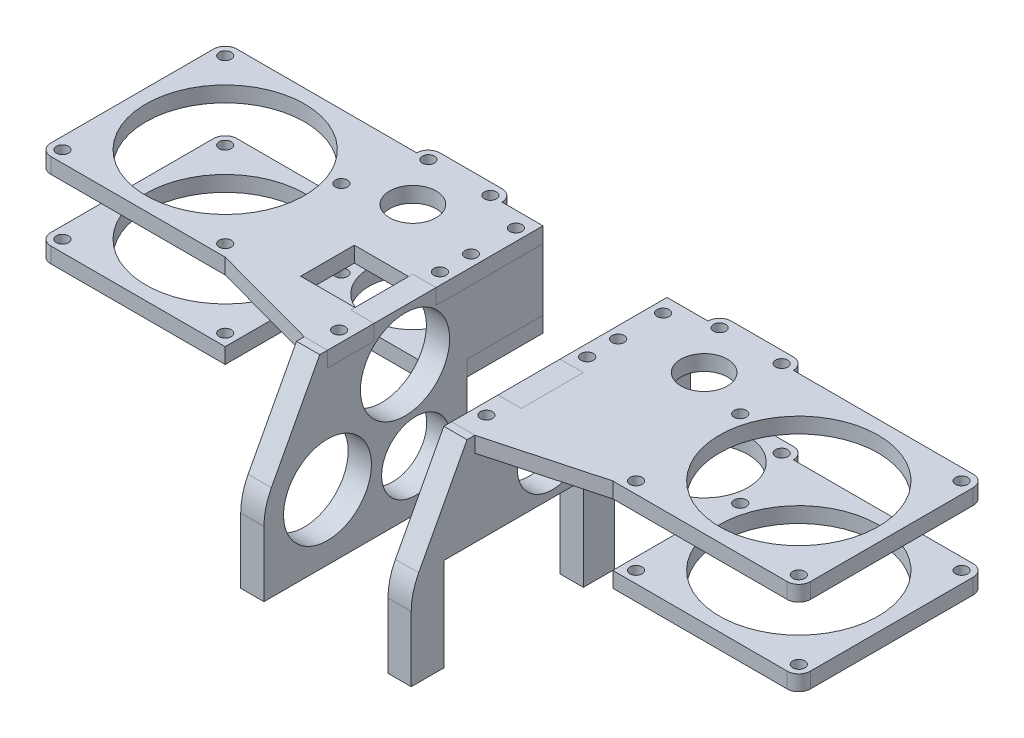
SolidWorks part; units mm, degrees
material "Alum Plate"
ref_plane "Front Plane" through (0, 0, 0) normal (0, 0, 1) x (1, 0, 0)
ref_plane "Top Plane" through (0, 0, 0) normal (0, 1, 0) x (1, 0, 0)
ref_plane "Right Plane" through (0, 0, 0) normal (1, 0, 0) x (0, 0, -1)
sketch "Sketch1" plane through (0, 0, 0) normal (0, 1, 0) x (1, 0, 0)
  line L0 (0, 0) -> (117.475, 0) construction
  line L1 (-117.475, 0) -> (0, 0) construction
  line L3 (-9.525, 165.735) -> (-3.175, 165.735)
  line L4 (-9.525, 165.735) -> (-9.525, 51.435)
  line L5 (-9.525, 51.435) -> (-3.175, 51.435)
  line L6 (-3.175, 165.735) -> (-3.175, 51.435)
  line L7 (-9.525, 165.735) -> (-3.175, 51.435) construction
  line L8 (-9.525, 51.435) -> (-3.175, 165.735) construction
  line L14 (-155.575, -76.2) -> (155.575, -76.2)
  line L20 (-25.4, 38.1) -> (0, 38.1) construction
  line L21 (-6.35, 108.585) -> (0, 108.585)
  line L29 (0, 0) -> (0, -18.415) construction
  line L30 (-117.475, 0) -> (-59.6589, 19.05) construction
  line L43 (59.6589, 19.05) -> (117.475, 0) construction
  line L44 (-86.6074, 10.1707) -> (-86.2044, 10.3034)
  line L55 (-77.1578, 13.2842) -> (-76.7548, 13.417)
  line L69 (-155.575, -76.2) -> (-155.575, 38.1)
  line L70 (-155.575, 38.1) -> (155.575, 38.1)
  line L71 (155.575, -76.2) -> (155.575, 38.1)
  line L78 (0, 108.585) -> (0, -18.415)
  line L79 (0, -18.415) -> (0, -145.415) construction
  line L80 (-9.525, -202.565) -> (-3.175, -202.565) construction
  line L81 (-9.525, -202.565) -> (-9.525, -88.265) construction
  line L82 (-9.525, -88.265) -> (-3.175, -88.265) construction
  line L83 (-3.175, -202.565) -> (-3.175, -88.265) construction
  line L84 (-9.525, -202.565) -> (-3.175, -88.265) construction
  line L85 (-9.525, -88.265) -> (-3.175, -202.565) construction
  line L86 (0, -145.415) -> (-6.35, -145.415) construction
  line L87 (-34.925, -76.2) -> (-25.4, -76.2)
  line L88 (-34.925, -76.2) -> (-34.925, 38.1)
  line L89 (-34.925, 38.1) -> (-25.4, 38.1)
  line L90 (-25.4, -76.2) -> (-25.4, 38.1)
  line L91 (34.925, -76.2) -> (25.4, -76.2)
  line L92 (34.925, -76.2) -> (34.925, 38.1)
  line L93 (34.925, 38.1) -> (25.4, 38.1)
  line L94 (25.4, -76.2) -> (25.4, 38.1)
  line L95 (0, 38.1) -> (25.4, 38.1) construction
  circle A0 centre (-117.475, 0) radius 32.5
  circle A1 centre (-117.475, 0) radius 25
  circle A2 centre (117.475, 0) radius 32.5
  circle A3 centre (117.475, 0) radius 25
  circle A4 centre (-59.6589, 19.05) radius 18
  circle A5 centre (59.6589, 19.05) radius 18
  circle A8 centre (-81.6811, 11.7938) radius 4.7625
  point P8 (-6.35, 108.585)
  point P21 (117.475, 32.5)
  point P25 (59.6589, 37.05)
  point P29 (59.6589, 1.05)
  point P31 (0, -76.2)
  point P32 (-6.35, -145.415)
  point P62 (149.975, 0)
  dimension "D1" = 50
  dimension "D2" = 65
  dimension "D8" = 36
  dimension "D11" = 127
  dimension "D12" = 56.515
  dimension "D16" = 9.525
  dimension "D3" = 114.3
  dimension "D4" = 6.35
  dimension "D5" = 234.95
  dimension "D6" = 38.1
  dimension "D7" = 38.1
  dimension "D9" = 114.3
  dimension "D10" = 9.525
  dimension "D13" = 9.525
  dimension "D14" = 50.8
  dimension "D15" = 60.8736
  dimension "D18" = 19.05
sketch "Sketch2" plane through (0, 0, 0) normal (1, 0, 0) x (0, 0, -1)
  line L0 (0, 25.4) -> (0, 56.175) construction
  line L1 (-32.5, 59.675) -> (32.5, 59.675)
  line L2 (-32.5, 59.675) -> (-32.5, 52.675)
  line L3 (-32.5, 52.675) -> (32.5, 52.675)
  line L4 (32.5, 59.675) -> (32.5, 52.675)
  line L5 (-32.5, 59.675) -> (32.5, 52.675) construction
  line L6 (-32.5, 52.675) -> (32.5, 59.675) construction
  line L7 (-32.5, 88.9) -> (32.5, 88.9)
  line L8 (-32.5, 88.9) -> (-32.5, 81.9)
  line L9 (-32.5, 81.9) -> (32.5, 81.9)
  line L10 (32.5, 88.9) -> (32.5, 81.9)
  line L11 (-32.5, 88.9) -> (32.5, 81.9) construction
  line L12 (-32.5, 81.9) -> (32.5, 88.9) construction
  line L13 (-25.8191, 0) -> (33.9817, 0) construction
  line L14 (-18.415, 69.85) -> (-145.415, 69.85)
  line L15 (-76.2, 90.775) -> (38.1, 90.775)
  line L16 (-76.2, 90.775) -> (-76.2, 52.675)
  line L17 (-76.2, 52.675) -> (38.1, 52.675)
  line L18 (38.1, 90.775) -> (38.1, 52.675)
  line L19 (-14, 35.2052) -> (-50.165, 41.275) construction
  line L20 (-50.165, 41.275) -> (-18.415, 69.85) construction
  line L21 (108.585, 0) -> (-18.415, 0) construction
  line L22 (-76.2, 84.425) -> (38.1, 84.425)
  line L23 (-76.2, 59.025) -> (38.1, 59.025)
  line L24 (-14, 35.2052) -> (-18.415, 69.85) construction
  line L25 (0, 35.2052) -> (0, 81.9) construction
  line L26 (-18.415, 69.85) -> (108.585, 69.85)
  line L32 (-76.2, 14.575) -> (38.1, 14.575)
  line L33 (-76.2, 14.575) -> (-76.2, 11.4)
  line L38 (-76.2, 11.4) -> (38.1, 11.4)
  line L39 (38.1, 14.575) -> (38.1, 11.4)
  line L40 (1.05, 39.9242) -> (37.05, 39.9242)
  line L41 (1.05, 39.9242) -> (1.05, 84.425)
  line L42 (1.05, 84.425) -> (37.05, 84.425)
  line L43 (37.05, 39.9242) -> (37.05, 84.425)
  line L44 (1.05, 39.9242) -> (37.05, 84.425) construction
  line L45 (1.05, 84.425) -> (37.05, 39.9242) construction
  line L46 (-38.1, 90.775) -> (-38.1, 52.675)
  line L47 (-38.1, 71.725) -> (0, 71.725) construction
  line L48 (0, 71.725) -> (38.1, 71.725) construction
  line L49 (-76.2, 14.575) -> (38.1, 11.4) construction
  line L50 (-76.2, 11.4) -> (38.1, 14.575) construction
  circle A0 centre (0, 25.4) radius 25.4
  circle A1 centre (-18.415, 69.85) radius 18.0086
  circle A2 centre (-14, 35.2052) radius 14
  circle A3 centre (-145.415, 69.85) radius 57.15
  circle A4 centre (-18.415, 69.85) radius 4.7625
  circle A5 centre (-50.165, 41.275) radius 18
  circle A6 centre (108.585, 69.85) radius 57.15
  point P2 (0, 56.175)
  point P8 (0, 85.4)
  point P16 (-32.165, 41.275)
  point P28 (-68.165, 41.275)
  point P32 (19.05, 62.1746)
  point P34 (-202.565, 69.85)
  point P35 (-28, 35.2052)
  point P36 (0, 35.2052)
  point P37 (-0.4064, 69.85)
  point P38 (-36.4236, 69.85)
  point P47 (0, 50.8)
  point P57 (-19.05, 12.9875)
  dimension "D1" = 50.8
  dimension "D8" = 36.0172
  dimension "D2" = 28
  dimension "D11" = 9.525
  dimension "D12" = 36
  dimension "D3" = 7
  dimension "D4" = 38.1
  dimension "D5" = 22.225
  dimension "D6" = 6.35
  dimension "D7" = 6.35
  dimension "D9" = 69.85
  dimension "D10" = 44.5008
  dimension "D13" = 19.05
  dimension "D14" = 31.75
  dimension "D15" = 3.175
  dimension "D16" = 25.4
  dimension "D17" = 34.925
  dimension "D18" = 38.1
  dimension "D19" = 28.575
sketch "Sketch5" plane through (0, 0, 0) normal (0, 1, 0) x (1, 0, 0)
  line L0 (-34.925, -76.2) -> (-34.925, 38.1) construction
  line L1 (-60.071, 0) -> (-28.575, 0)
  line L2 (-60.071, 0) -> (-60.071, -28)
  line L3 (-60.071, -28) -> (-28.575, -28)
  line L4 (-28.575, 0) -> (-28.575, -28)
  line L5 (-60.071, 0) -> (-28.575, -28) construction
  line L6 (-60.071, -28) -> (-28.575, 0) construction
  line L7 (-74.93, -32.165) -> (-34.925, -32.165)
  line L8 (-74.93, -32.165) -> (-74.93, -68.165)
  line L9 (-74.93, -68.165) -> (-34.925, -68.165)
  line L10 (-34.925, -32.165) -> (-34.925, -68.165)
  line L11 (-74.93, -32.165) -> (-34.925, -68.165) construction
  line L12 (-74.93, -68.165) -> (-34.925, -32.165) construction
  line L13 (-60.071, -0.4064) -> (-20.066, -0.4064)
  line L14 (-60.071, -0.4064) -> (-60.071, -36.4236)
  line L15 (-60.071, -36.4236) -> (-20.066, -36.4236)
  line L16 (-20.066, -0.4064) -> (-20.066, -36.4236)
  line L17 (-60.071, -0.4064) -> (-20.066, -36.4236) construction
  line L18 (-60.071, -36.4236) -> (-20.066, -0.4064) construction
  line L20 (-25.4, -76.2) -> (-25.4, 38.1) construction
  point P0 (-44.323, -14)
  point P5 (-54.9275, -50.165)
  point P10 (-40.0685, -18.415)
  dimension "D1" = 3.175
  dimension "D2" = 31.496
  dimension "D5" = 40.005
  dimension "D6" = 40.005
ref_plane "Plane1" through (0, 84.425, 0) normal (0, 1, 0) x (1, 0, 0)
ref_plane "Plane2" through (0, 59.025, 0) normal (0, -1, 0) x (-1, 0, 0)
ref_plane "Plane3" through (25.4, 0, 0) normal (1, 0, 0) x (0, 0, -1)
sketch "Sketch6" plane through (25.4, 0, 0) normal (1, 0, 0) x (0, 0, -1)
  line L0 (-18.415, 90.775) -> (-18.415, 69.85) construction
  line L2 (-73.1546, 53.4938) -> (-53.34, 90.775)
  line L3 (-76.2, 90.775) -> (38.1, 90.775) construction
  line L4 (-53.34, 90.775) -> (-50.165, 90.775)
  line L5 (-50.165, 90.775) -> (-50.165, 84.425)
  line L6 (-76.2, 84.425) -> (38.1, 84.425) construction
  line L7 (-50.165, 84.425) -> (-31.115, 84.425)
  line L8 (6.985, 59.025) -> (6.985, 14.575)
  line L10 (-76.2, 14.575) -> (38.1, 14.575) construction
  line L11 (-76.2, 14.575) -> (-76.2, 41.275)
  line L12 (-76.2, 14.575) -> (6.985, 14.575)
  line L13 (-31.115, 84.425) -> (-31.115, 90.775)
  line L14 (-31.115, 90.775) -> (-5.715, 90.775)
  line L15 (-5.715, 84.425) -> (-5.715, 90.775)
  line L16 (-31.115, 84.425) -> (-5.715, 90.775) construction
  line L17 (-31.115, 90.775) -> (-5.715, 84.425) construction
  line L18 (-5.715, 84.425) -> (6.985, 84.425)
  line L19 (-76.2, 59.025) -> (38.1, 59.025) construction
  line L20 (6.985, 59.025) -> (38.1, 59.025)
  line L21 (6.985, 59.025) -> (6.985, 84.425) construction
  line L22 (6.985, 84.425) -> (38.1, 84.425)
  line L23 (38.1, 59.025) -> (38.1, 84.425)
  line L24 (6.985, 59.025) -> (38.1, 84.425) construction
  line L25 (6.985, 84.425) -> (38.1, 59.025) construction
  line L26 (6.985, 84.425) -> (6.985, 59.025) construction
  arc A3 (-76.2, 41.275) -> (-73.1546, 53.4938) centre (-50.165, 41.275) cw
  point P10 (-18.415, 87.6)
  point P28 (22.5425, 71.725)
  dimension "D1" = 25.4
  dimension "D2" = 31.75
  dimension "D3" = 3.175
  dimension "D4" = 25.4
extrude "Boss-Extrude1" add sketch "Sketch6" along normal up to vertex (9.525 mm away) up to point (34.925, 0, -38.1)
sketch "Sketch7" plane through (0, 84.425, 0) normal (0, 1, 0) x (1, 0, 0)
  line L0 (25.4, -50.165) -> (34.925, -50.165)
  line L2 (155.575, -76.2) -> (155.575, 38.1) construction
  line L3 (155.575, -38.1) -> (155.575, 38.1)
  line L4 (155.575, 38.1) -> (25.4, 38.1)
  line L5 (25.4, 38.1) -> (25.4, -5.715)
  line L6 (155.575, -38.1) -> (79.375, -38.1)
  line L7 (79.375, -38.1) -> (34.925, -50.165)
  line L8 (117.475, 38.1) -> (117.475, 0) construction
  line L9 (117.475, 0) -> (117.475, -38.1) construction
  line L10 (25.4, -31.115) -> (34.925, -31.115)
  line L11 (34.925, -31.115) -> (34.925, -5.715)
  line L12 (34.925, -5.715) -> (25.4, -5.715)
  line L13 (25.4, -76.2) -> (25.4, 38.1) construction
  line L14 (25.4, -31.115) -> (25.4, -50.165)
  circle A0 centre (117.475, 0) radius 32.5 construction
  circle A1 centre (117.475, 0) radius 32.5
  circle A3 centre (59.6589, 19.05) radius 9.525
  point P28 (25.4, -5.715)
  point P31 (25.4, -5.715)
  dimension "D2" = 19.05
extrude "Boss-Extrude2" add sketch "Sketch7" along normal up to surface (6.35 mm away) separate body up to face at (30.1625, 90.775, 51.7525)
sketch "Sketch8" plane through (0, 59.025, 0) normal (0, -1, 0) x (-1, 0, 0)
  line L1 (-79.375, -38.1) -> (-155.575, -38.1)
  line L2 (-79.375, -38.1) -> (-79.375, 38.1) construction
  line L3 (-79.375, 38.1) -> (-155.575, 38.1)
  line L4 (-155.575, -38.1) -> (-155.575, 38.1)
  line L5 (-79.375, -38.1) -> (-155.575, 38.1) construction
  line L6 (-79.375, 38.1) -> (-155.575, -38.1) construction
  line L7 (155.575, 38.1) -> (-155.575, 38.1) construction
  line L8 (-25.4, 38.1) -> (-79.375, 38.1)
  line L12 (-79.375, -38.1) -> (-79.375, -3.175)
  line L13 (-79.375, -3.175) -> (-34.925, -3.175)
  line L14 (-34.925, -76.2) -> (-34.925, 38.1) construction
  line L15 (-34.925, -3.175) -> (-34.925, 6.985)
  line L16 (-34.925, 6.985) -> (-25.4, 6.985)
  line L17 (-25.4, 6.985) -> (-25.4, 38.1)
  circle A0 centre (-117.475, 0) radius 32.5 construction
  circle A1 centre (-117.475, 0) radius 32.5
  circle A3 centre (-59.6589, 19.05) radius 18
  circle A4 centre (-59.6589, 19.05) radius 18 construction
  dimension "D1" = 22.225
extrude "Boss-Extrude3" add sketch "Sketch8" along normal up to vertex (6.35 mm away) separate body up to point (0, 52.675, -38.1)
sketch "Sketch14" plane through (0, 59.025, 0) normal (0, 1, 0) x (1, 0, 0)
  line L0 (59.6589, 38.1) -> (59.6589, 19.05) construction
  line L1 (72.3589, 42.8625) -> (46.9589, 42.8625)
  line L2 (25.4, 38.1) -> (155.575, 38.1) construction
  line L3 (67.5964, 38.1) -> (51.7214, 38.1)
  arc A0 (67.5964, 38.1) -> (72.3589, 42.8625) centre (72.3589, 38.1) ccw
  arc A1 (46.9589, 42.8625) -> (51.7214, 38.1) centre (46.9589, 38.1) ccw
  arc A2 (72.3589, 42.8625) -> (67.5964, 38.1) centre (72.3589, 38.1) ccw construction
  arc A3 (51.7214, 38.1) -> (46.9589, 42.8625) centre (46.9589, 38.1) ccw construction
  point P10 (66.9244, 38.1)
  dimension "D1" = 9.525
  dimension "D2" = 25.4
extrude "Boss-Extrude4" add sketch "Sketch14" against normal up to surface (6.35 mm away) up to face at (117.475, 52.675, -32.5)
extrude "Boss-Extrude5" add sketch "Sketch14<2>" against normal up to surface (-25.4 mm away) from surface up to face at (59.69, 84.425, 17.399) starting at face at (59.6589, 90.775, -28.575)
sketch "Sketch14<2>" plane through (0, 59.025, 0) normal (0, 1, 0) x (1, 0, 0) same geometry as "Sketch14"
sketch "Sketch15" plane through (0, 52.675, 0) normal (0, -1, 0) x (1, 0, 0)
  line L0 (-81.6811, -11.7938) -> (81.6811, -11.7938) construction
  line L1 (59.6589, -19.05) -> (117.475, 0) construction
  line L2 (79.375, 38.1) -> (79.375, 3.175) construction
  line L3 (155.575, 38.1) -> (79.375, 38.1) construction
  line L4 (155.575, 76.2) -> (155.575, -38.1) construction
  line L5 (-155.575, -38.1) -> (155.575, -38.1) construction
  line L6 (150.8125, 38.1) -> (155.575, 38.1)
  line L7 (155.575, 38.1) -> (155.575, 33.3375)
  line L8 (150.8125, -38.1) -> (155.575, -38.1)
  line L9 (155.575, -38.1) -> (155.575, -33.3375)
  line L10 (30.1625, -38.1) -> (30.1625, -31.75) construction
  line L11 (30.1625, -31.75) -> (30.1625, -13.335) construction
  line L12 (30.1625, -13.335) -> (30.1625, -6.985) construction
  line L13 (34.925, -6.985) -> (25.4, -6.985) construction
  line L14 (30.1625, 5.715) -> (30.1625, -0.635) construction
  line L15 (30.1625, 31.115) -> (30.1625, 40.64) construction
  line L16 (30.1625, 40.64) -> (30.1625, 50.165) construction
  line L17 (34.925, 50.165) -> (25.4, 50.165) construction
  line L18 (34.925, 31.115) -> (25.4, 31.115) construction
  line L19 (34.925, 5.715) -> (25.4, 5.715) construction
  line L20 (30.1625, -6.985) -> (30.1625, -0.635) construction
  circle A0 centre (46.9589, -38.1) radius 2.4892
  circle A1 centre (72.3589, -38.1) radius 2.4892
  circle A3 centre (81.6811, -11.7938) radius 2.4892
  circle A4 centre (150.8125, -33.3375) radius 2.4892
  circle A5 centre (150.8125, 33.3375) radius 2.4892
  circle A6 centre (84.1375, 33.3375) radius 2.4892
  circle A7 centre (84.1375, 33.3375) radius 4.7625 construction
  arc A8 (155.575, 33.3375) -> (150.8125, 38.1) centre (150.8125, 33.3375) ccw
  arc A9 (150.8125, -38.1) -> (155.575, -33.3375) centre (150.8125, -33.3375) ccw
  arc A10 (155.575, -33.3375) -> (150.8125, -38.1) centre (150.8125, -33.3375) ccw construction
  arc A11 (150.8125, 38.1) -> (155.575, 33.3375) centre (150.8125, 33.3375) ccw construction
  circle A12 centre (30.1625, -31.75) radius 2.4892
  circle A13 centre (30.1625, -13.335) radius 2.4892
  circle A14 centre (30.1625, -0.635) radius 2.4892
  circle A15 centre (30.1625, 40.64) radius 2.4892
  dimension "D1" = 4.9784
  dimension "D2" = 9.525
  dimension "D3" = 6.35
  dimension "D4" = 6.35
extrude "Cut-Extrude9" cut sketch "Sketch15" against normal through all
mirror "Mirror2" about plane through (0, 0, 0) normal (1, 0, 0) of bodies 106 122 121 108 111
sketch "Sketch10" plane through (-25.4, 0, 0) normal (1, 0, 0) x (0, 0, -1)
  circle A0 centre (-50.165, 41.275) radius 18 construction
  circle A1 centre (-50.165, 41.275) radius 18
  circle A2 centre (-14, 35.2052) radius 14 construction
  circle A3 centre (-14, 35.2052) radius 14
extrude "Cut-Extrude2" cut sketch "Sketch10" against normal through all
sketch "Sketch11" plane through (-34.925, 0, 0) normal (-1, 0, 0) x (0, 0, 1)
  circle A1 centre (18.415, 69.85) radius 18.2626
  circle A4 centre (18.415, 69.85) radius 18.0086 construction
  dimension "D1" = 0.254
extrude "Cut-Extrude6" cut sketch "Sketch11" against normal through all
sketch "Sketch12" plane through (0, 84.425, 0) normal (0, -1, 0) x (1, 0, 0)
  line L1 (-34.925, 7.4108) -> (-57.15, 7.4108)
  line L2 (-34.925, 7.4108) -> (-34.925, 29.4192)
  line L3 (-34.925, 29.4192) -> (-57.15, 29.4192)
  line L4 (-57.15, 7.4108) -> (-57.15, 29.4192)
  line L5 (-34.925, 7.4108) -> (-57.15, 29.4192) construction
  line L6 (-34.925, 29.4192) -> (-57.15, 7.4108) construction
  line L8 (-34.925, 5.715) -> (-34.925, 31.115) construction
  line L10 (-34.925, 5.715) -> (-34.925, 31.115) construction
  point P4 (-46.0375, 18.415)
  point P5 (0, 0)
  point P6 (0, 0)
  point P15 (-34.925, 11.1928)
  point P16 (-34.925, 27.8869)
  point P19 (0, 0)
  point P23 (0, 0)
  dimension "D1" = 22.225
extrude "Cut-Extrude7" cut sketch "Sketch12" against normal through all
sketch "Sketch13" plane through (25.4, 0, 0) normal (-1, 0, 0) x (0, 0, 1)
  circle A0 centre (18.415, 69.85) radius 14.2875
  dimension "D1" = 28.575
extrude "Cut-Extrude8" cut sketch "Sketch13" against normal up to next (9.525 mm away)
sketch "Sketch16" plane through (34.925, 0, 0) normal (1, 0, 0) x (0, 0, -1)
  line L0 (-76.2, 14.575) -> (6.985, 14.575) construction
  line L1 (-62.865, 14.575) -> (-5.715, 14.575)
  line L2 (-62.865, 14.575) -> (-62.865, 52.675)
  line L3 (-62.865, 52.675) -> (-5.715, 52.675)
  line L4 (-5.715, 14.575) -> (-5.715, 52.675)
  line L5 (-62.865, 14.575) -> (-5.715, 52.675) construction
  line L6 (-62.865, 52.675) -> (-5.715, 14.575) construction
  line L7 (33.3375, 52.675) -> (-33.3375, 52.675) construction
  line L8 (6.985, 14.575) -> (6.985, 59.025) construction
  point P4 (-34.29, 33.625)
  dimension "D1" = 12.7
  dimension "D2" = 57.15
extrude "Cut-Extrude10" cut sketch "Sketch16" against normal up to next (9.525 mm away)
